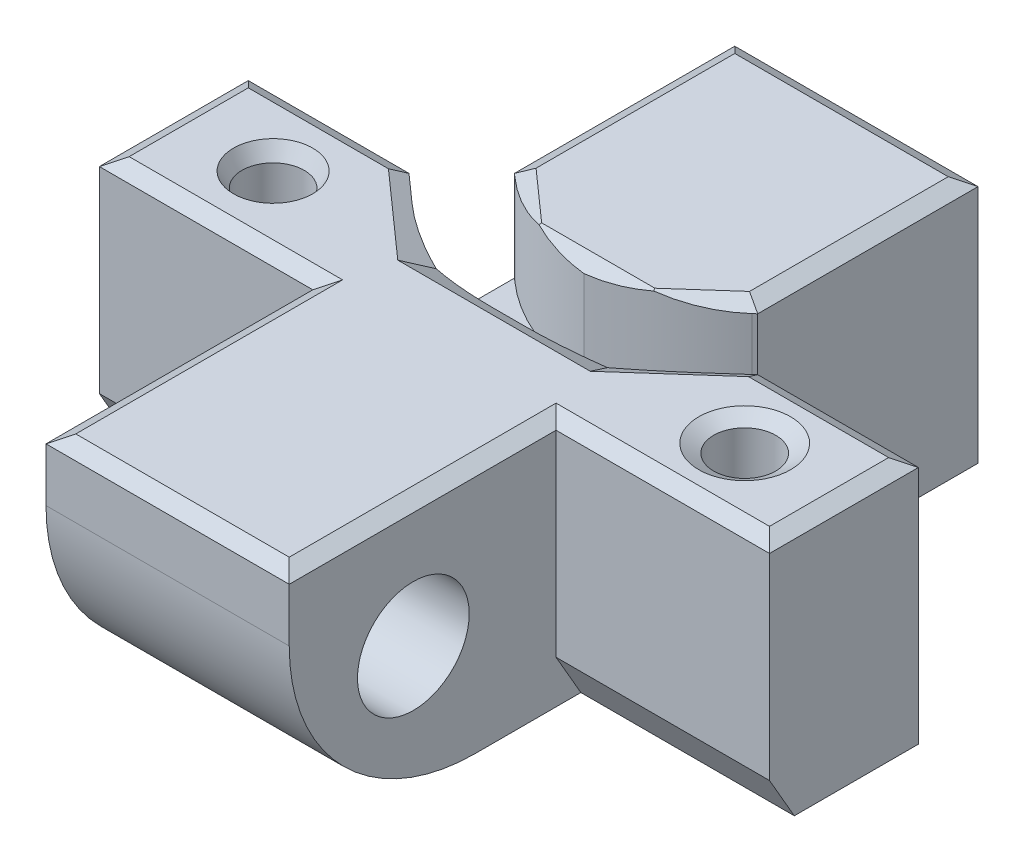
SolidWorks part; units mm, degrees
material "ﾎﾟﾘｴｽﾃﾙ樹脂"
ref_plane "正面" through (0, 0, 0) normal (0, 0, 1) x (1, 0, 0)
ref_plane "平面" through (0, 0, 0) normal (0, 1, 0) x (1, 0, 0)
ref_plane "右側面" through (0, 0, 0) normal (1, 0, 0) x (0, 0, -1)
sketch "ｽｹｯﾁ1" plane through (0, 0, 0) normal (0, 1, 0) x (1, 0, 0)
  line L0 (0, 13.875) -> (0, -13.875) construction
  line L1 (-4.9, -13.875) -> (4.9, -13.875)
  line L2 (-4.9, -13.875) -> (-4.9, 13.875)
  line L3 (-4.9, 13.875) -> (4.9, 13.875)
  line L4 (4.9, -13.875) -> (4.9, 13.875)
  line L5 (-4.9, -13.875) -> (4.9, 13.875) construction
  line L6 (-4.9, 13.875) -> (4.9, -13.875) construction
  line L7 (-4.9, 0) -> (4.9, 0) construction
  line L9 (-13.5, -3.125) -> (13.5, -3.125)
  line L10 (-13.5, -3.125) -> (-13.5, 2.875)
  line L11 (-13.5, 2.875) -> (13.5, 2.875)
  line L12 (13.5, -3.125) -> (13.5, 2.875)
  line L13 (-13.5, -3.125) -> (13.5, 2.875) construction
  line L14 (-13.5, 2.875) -> (13.5, -3.125) construction
  circle A0 centre (9.5, -0.125) radius 1.25
  circle A1 centre (-9.5, -0.125) radius 1.25
  point P0 (0, 0)
  point P10 (0, -0.125)
  dimension "D6" = 19
  dimension "D7" = 2.5
  dimension "D8" = 3
  dimension "D1" = 27.75
  dimension "D2" = 9.8
  dimension "D3" = 27
  dimension "D4" = 6
  dimension "D5" = 11
extrude "ﾎﾞｽ - 押し出し1" add sketch "ｽｹｯﾁ1" along normal blind 10 contours L2 L11 L4 L3 | L9 L12 L11 L4 A0 | L11 L2 L9 L4 | L11 L10 L9 L2 A1 | L9 L2 L1 L4
sketch "ｽｹｯﾁ3" plane through (4.9, 0, 0) normal (1, 0, 0) x (0, 0, -1)
  line L0 (-13.875, 5) -> (13.875, 5) construction
  line L1 (-13.875, 10) -> (-13.875, 0) construction
  line L2 (13.875, 10) -> (13.875, 0) construction
  circle A0 centre (-8.875, 5) radius 2.25
  dimension "D1" = 5
  dimension "D2" = 4.5
extrude "ｶｯﾄ - 押し出し2" cut sketch "ｽｹｯﾁ3" against normal through all
sketch "ｽｹｯﾁ5" plane through (0, 10, 0) normal (0, 1, 0) x (1, 0, 0)
  line L0 (0, 0) -> (0, 50000) construction
  line L1 (4.9, 5) -> (2.5089, 2.875)
  line L2 (4.9, 2.875) -> (4.9, 13.875) construction
  line L3 (2.5089, 2.875) -> (-2.5089, 2.875)
  line L4 (7.025, 2.875) -> (3.6493, -0.125)
  line L5 (4.9, 2.875) -> (13.5, 2.875) construction
  line L6 (3.6493, -0.125) -> (-3.6493, -0.125)
  line L7 (-4.9, 13.875) -> (4.9, 13.875) construction
  line L8 (4.9, 5) -> (4.9, 2.875)
  line L9 (4.9, 2.875) -> (7.025, 2.875)
  line L10 (-7.025, 2.875) -> (-3.6493, -0.125)
  line L11 (-4.9, 5) -> (-2.5089, 2.875)
  line L12 (-4.9, 5) -> (-4.9, 2.875)
  line L13 (-4.9, 2.875) -> (-7.025, 2.875)
  point P18 (0, -0.125)
  point P19 (0, 2.875)
  dimension "D1" = 3
  dimension "D2" = 3
  dimension "D3" = 2.125
  dimension "D4" = 11
  dimension "D5" = 2.125
extrude "ｶｯﾄ - 押し出し3" cut sketch "ｽｹｯﾁ5" against normal blind 4
fillet "ﾌｨﾚｯﾄ2" radius 7.5 1 edges at (0, 0, 13.875)
chamfer "面取り1" distance 0.6 angle 30 20 edges at (-10.2625, 10, -2.875) (-13.5, 10, 0.125) (-9.2, 10, 3.125) (-4.9, 10, 8.5) (0, 10, 13.875) (4.9, 10, 8.5) (9.2, 10, 3.125) (13.5, 10, 0.125) (-4.9, 10, -9.4375) (10.2625, 10, -2.875) (4.9, 10, -9.4375) (0, 10, -13.875) (3.7044, 10, -3.9375) (0, 10, -2.875) (-3.7044, 10, -3.9375) (-5.3372, 10, -1.375) (0, 10, 0.125) (5.3372, 10, -1.375) (9.5, 10, 1.375) (-9.5, 10, 1.375)
fillet "ﾌｨﾚｯﾄ3" radius 8 4 edges at (-3.6493, 7.8268, 0.125) (3.6493, 7.8268, 0.125) (2.5089, 7.8268, -2.875) (-2.5089, 7.8268, -2.875)
chamfer "面取り3" distance 1 angle 60 2 edges at (-9.2, 0, 3.125) (9.2, 0, 3.125)
